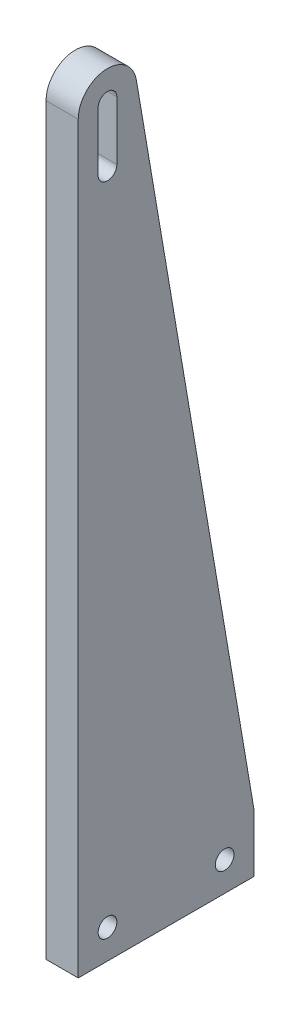
SolidWorks part; units mm, degrees
ref_plane "Front Plane" through (0, 0, 0) normal (0, 0, 1) x (1, 0, 0)
ref_plane "Top Plane" through (0, 0, 0) normal (0, 1, 0) x (1, 0, 0)
ref_plane "Right Plane" through (0, 0, 0) normal (1, 0, 0) x (0, 0, -1)
sketch "Sketch1" plane through (0, 0, 0) normal (1, 0, 0) x (0, 0, -1)
  line L0 (0, 0) -> (30, 0)
  line L1 (30, 0) -> (30, 10)
  line L2 (30, 10) -> (9.929, 127.8395)
  line L3 (0, 0) -> (0, 127)
  line L4 (5, 117) -> (5, 127) construction
  line L5 (3.4, 117) -> (3.4, 127)
  line L6 (6.6, 117) -> (6.6, 127)
  line L7 (30, 10) -> (0, 10) construction
  line L8 (15, 10) -> (15, 0) construction
  line L9 (5, 5) -> (25, 5) construction
  arc A0 (0, 127) -> (9.929, 127.8395) centre (5, 127) cw
  arc A1 (3.4, 117) -> (6.6, 117) centre (5, 117) ccw
  arc A2 (6.6, 127) -> (3.4, 127) centre (5, 127) ccw
  circle A3 centre (5, 5) radius 1.6
  circle A4 centre (25, 5) radius 1.6
  point P9 (5, 122)
  point P20 (15, 5)
  dimension "D7" = 3.2
  dimension "D1" = 10
  dimension "D2" = 30
  dimension "D3" = 10
  dimension "D4" = 3.2
  dimension "D5" = 122
  dimension "D6" = 5
  dimension "D8" = 20
extrude "Boss-Extrude1" add sketch "Sketch1" along normal blind 5.4864
